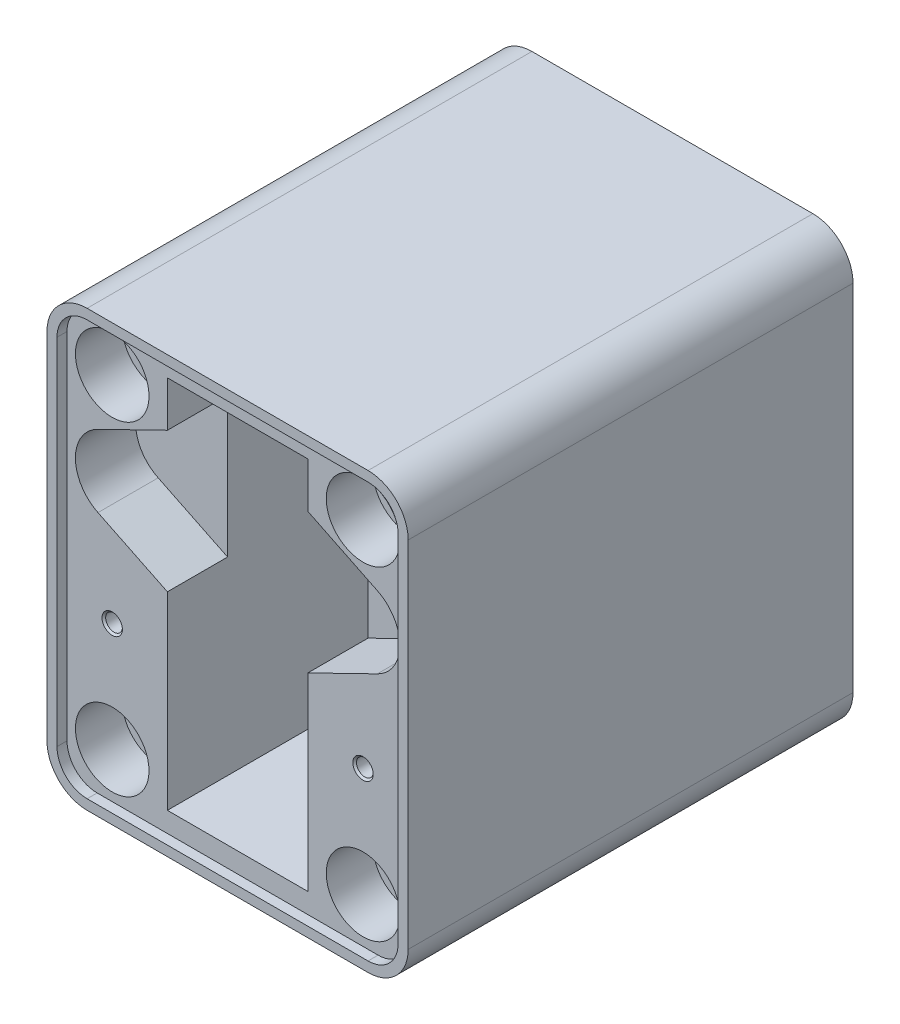
SolidWorks part; units mm, degrees
ref_plane "Front Plane" through (0, 0, 0) normal (0, 0, 1) x (1, 0, 0)
ref_plane "Top Plane" through (0, 0, 0) normal (0, 1, 0) x (1, 0, 0)
ref_plane "Right Plane" through (0, 0, 0) normal (1, 0, 0) x (0, 0, -1)
sketch "Sketch1" plane through (0, 0, 0) normal (0, 0, 1) x (1, 0, 0)
  line L1 (0, 0) -> (54, 0)
  line L2 (0, 0) -> (0, 65)
  line L3 (0, 65) -> (54, 65)
  line L4 (54, 0) -> (54, 65)
  dimension "D1" = 65
  dimension "D2" = 54
extrude "Boss-Extrude1" add sketch "Sketch1" along normal blind 65 contours L2 L1 L4 L3
sketch "Sketch2" plane through (0, 0, 65) normal (0, 0, 1) x (1, 0, 0)
  line L1 (16.5, 53.25) -> (37.5, 53.25)
  line L2 (16.5, 53.25) -> (16.5, 11.75)
  line L3 (16.5, 11.75) -> (37.5, 11.75)
  line L4 (37.5, 53.25) -> (37.5, 11.75)
  line L6 (0, 65) -> (0, 0) construction
  line L7 (54, 65) -> (0, 65) construction
  dimension "D1" = 41.5
  dimension "D2" = 21
  dimension "D3" = 16.5
  dimension "D4" = 11.75
extrude "Cut-Extrude1" cut sketch "Sketch2" against normal through all contours L2 L3 L4 L1
fillet "Fillet1" radius 6 4 edges at (0, 65, 32.5) (0, 0, 32.5) (54, 65, 32.5) (54, 0, 32.5)
sketch "Sketch3" plane through (0, 0, 65) normal (0, 0, 1) x (1, 0, 0)
  line L0 (16.5, 53.25) -> (37.5, 53.25) construction
  line L1 (16.5, 60.5) -> (37.5, 60.5)
  line L2 (16.5, 60.5) -> (16.5, 4.5)
  line L3 (16.5, 4.5) -> (37.5, 4.5)
  line L4 (37.5, 60.5) -> (37.5, 4.5)
  line L5 (16.5, 11.75) -> (37.5, 11.75) construction
  line L6 (37.5, 53.25) -> (37.5, 11.75) construction
  line L7 (16.5, 53.25) -> (16.5, 11.75) construction
  dimension "D1" = 7.25
  dimension "D2" = 7.25
extrude "Cut-Extrude2" cut sketch "Sketch3" against normal blind 32
sketch "Sketch4" plane through (0, 0, 65) normal (0, 0, 1) x (1, 0, 0)
  line L0 (16.5, 53.25) -> (37.5, 53.25) construction
  line L1 (27, 43.25) -> (27, 20.577) construction
  line L2 (8.75, 43.25) -> (45.25, 43.25) construction
  line L3 (32.9178, 55.3838) -> (47.661, 48.1934)
  line L4 (47.661, 38.3066) -> (32.9178, 31.1162)
  line L5 (21.0822, 31.1162) -> (6.339, 38.3066)
  line L6 (6.339, 48.1934) -> (21.0822, 55.3838)
  arc A0 (21.0822, 31.1162) -> (32.9178, 31.1162) centre (27, 43.25) ccw
  arc A1 (47.661, 38.3066) -> (47.661, 48.1934) centre (45.25, 43.25) ccw
  arc A2 (13.7106, 40.8747) -> (14.25, 43.25) centre (8.75, 43.25) ccw construction
  arc A3 (32.9178, 55.3838) -> (21.0822, 55.3838) centre (27, 43.25) ccw
  arc A4 (13.7106, 45.6253) -> (13.7106, 40.8747) centre (27, 43.25) ccw construction
  arc A5 (6.339, 48.1934) -> (6.339, 38.3066) centre (8.75, 43.25) ccw
  dimension "D4" = 27
  dimension "D5" = 11
  dimension "D6" = 5.5
  dimension "D1" = 10
  dimension "D2" = 36.5
  dimension "D3" = 27
extrude "Cut-Extrude-Thin3" cut sketch "Sketch4" against normal blind 9 thin thin type one direction wall 0.5
extrude "Cut-Extrude3" cut sketch "Sketch4<3>" against normal blind 9
sketch "Sketch4<3>" plane through (0, 0, 65) normal (0, 0, 1) x (1, 0, 0) same geometry as "Sketch4"
hole_wizard "M3 Tapped Hole1" positions "3DSketch2" profile "Sketch7" tap size "M3" standard "ISO" end condition through all
sketch3d "3DSketch2"
  line L1 (16.5, 60.5, 33) -> (16.5, 53.25, 33) construction
  line L6 (16.5, 53.25, 33) -> (37.5, 53.25, 33) construction
  point P0 (22, 56.85, 33)
  point P2 (32, 56.85, 33)
  point P4 (32, 8.15, 33)
  point P6 (22, 8.15, 33)
  dimension "D1" = 10
  dimension "D2" = 5.5
  dimension "D3" = 48.7
  dimension "D4" = 3.6
cosmetic thread "Hole Thread3" parameters "D2"=3
cosmetic thread "Hole Thread4" parameters "D2"=3
cosmetic thread "Hole Thread5" parameters "D2"=3
cosmetic thread "Hole Thread6" parameters "D2"=3
sketch "Sketch7" plane through (22, 56.85, 33) normal (1, 0, 0) x (0, -1, 0)
  line L0 (0, 0) -> (0, 33)
  line L1 (0, 33) -> (1.25, 33)
  line L2 (1.25, 33) -> (1.25, 0.275)
  line L3 (1.25, 0.275) -> (1.525, 0)
  line L5 (1.525, 0) -> (0, 0)
  line L6 (-1.25, 0.275) -> (-1.525, 0) construction
  line L11 (0, -6.35) -> (0, 107.95) construction
  dimension "Thru Tap Drill Dia." = 2.5
  dimension "Thru Tap Drill Depth" = 33
  dimension "Near C'Sink Dia." = 3.05
  dimension "Near C'Sink Angle" = 90
hole_wizard "Hole1" positions "3DSketch3" profile "Sketch9" legacy end condition through all
sketch3d "3DSketch3"
  line L1 (0, 59, 65) -> (0, 6, 65) construction
  line L3 (48, 65, 65) -> (6, 65, 65) construction
  line L5 (37.5, 60.5, 65) -> (37.5, 53.7053, 65) construction
  line L6 (37.5, 32.7947, 65) -> (37.5, 4.5, 65) construction
  line L7 (6, 0, 65) -> (48, 0, 65) construction
  point P0 (8.25, 56.75, 65)
  point P2 (45.75, 56.75, 65)
  point P4 (45.75, 8.25, 65)
  point P6 (8.25, 8.25, 65)
  dimension "D1" = 8.25
  dimension "D2" = 8.25
  dimension "D3" = 8.25
  dimension "D4" = 8.25
  dimension "D5" = 8.25
  dimension "D6" = 8.25
sketch "Sketch9" plane through (8.25, 56.75, 65) normal (1, 0, 0) x (0, -1, 0)
  line L0 (0, 0) -> (0, 65)
  line L1 (0, 65) -> (3.25, 65)
  line L2 (3.25, 65) -> (3.25, 7)
  line L3 (3.25, 7) -> (5.5, 7)
  line L4 (5.5, 7) -> (5.5, 0)
  line L5 (5.5, 0) -> (0, 0)
  line L6 (0, 110) -> (0, -10) construction
  dimension "Diameter" = 6.5
  dimension "Depth" = 65
  dimension "C-Bore Diameter" = 11
  dimension "C-Bore Depth" = 7
sketch "Sketch10" plane through (0, 0, 65) normal (0, 0, 1) x (1, 0, 0)
  line L4 (48, 65) -> (6, 65)
  line L5 (0, 59) -> (0, 6)
  line L6 (6, 0) -> (48, 0)
  line L7 (54, 6) -> (54, 59)
  line L8 (48, 65) -> (6, 65)
  line L9 (0, 59) -> (0, 6)
  line L10 (6, 0) -> (48, 0)
  line L11 (54, 6) -> (54, 59)
  arc A4 (6, 65) -> (0, 59) centre (6, 59) ccw
  arc A5 (0, 6) -> (6, 0) centre (6, 6) ccw
  arc A6 (48, 0) -> (54, 6) centre (48, 6) ccw
  arc A7 (54, 59) -> (48, 65) centre (48, 59) ccw
  arc A8 (6, 65) -> (0, 59) centre (6, 59) ccw
  arc A9 (0, 6) -> (6, 0) centre (6, 6) ccw
  arc A10 (48, 0) -> (54, 6) centre (48, 6) ccw
  arc A11 (54, 59) -> (48, 65) centre (48, 59) ccw
  dimension "D1" = 0
extrude "Extrude-Thin1" add sketch "Sketch10" along normal blind 1.5 thin thin type one direction reverse wall 1.5
hole_wizard "M3 Tapped Hole2" positions "3DSketch4" profile "Sketch11" tap size "M3" standard "ISO" end condition through all
sketch3d "3DSketch4"
  line L0 (16.5, 32.7947, 65) -> (16.5, 4.5, 65) construction
  line L1 (37.5, 32.7947, 65) -> (37.5, 4.5, 65) construction
  point P0 (8.25, 24.5509, 65)
  point P2 (45.75, 24.5509, 65)
  dimension "D1" = 8.25
  dimension "D2" = 8.25
sketch "Sketch11" plane through (8.25, 24.5509, 65) normal (1, 0, 0) x (0, -1, 0)
  line L0 (0, 0) -> (0, 65)
  line L1 (0, 65) -> (1.25, 65)
  line L2 (1.25, 65) -> (1.25, 0.275)
  line L3 (1.25, 0.275) -> (1.525, 0)
  line L5 (1.525, 0) -> (0, 0)
  line L6 (-1.25, 0.275) -> (-1.525, 0) construction
  line L11 (0, -6.35) -> (0, 107.95) construction
  dimension "Thru Tap Drill Dia." = 2.5
  dimension "Thru Tap Drill Depth" = 65
  dimension "Near C'Sink Dia." = 3.05
  dimension "Near C'Sink Angle" = 90
cosmetic thread "Hole Thread7" parameters "D2"=3
cosmetic thread "Hole Thread8" parameters "D2"=3
